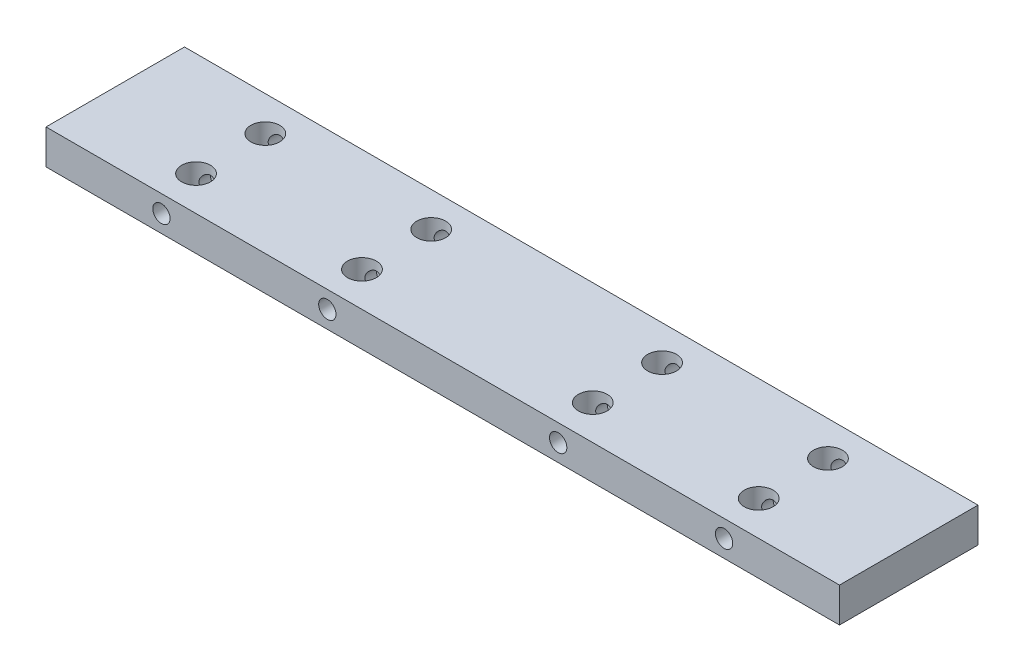
SolidWorks part; units mm, degrees
material "HDPE-green"
ref_plane "Front Plane" through (0, 0, 0) normal (0, 0, 1) x (1, 0, 0)
ref_plane "Top Plane" through (0, 0, 0) normal (0, 1, 0) x (1, 0, 0)
ref_plane "Right Plane" through (0, 0, 0) normal (1, 0, 0) x (0, 0, -1)
sketch "Sketch1" plane through (0, 0, 0) normal (0, 1, 0) x (1, 0, 0)
  line L1 (137.5, -24) -> (-137.5, -24)
  line L2 (137.5, -24) -> (137.5, 24)
  line L3 (137.5, 24) -> (-137.5, 24)
  line L4 (-137.5, -24) -> (-137.5, 24)
  line L5 (137.5, -24) -> (-137.5, 24) construction
  line L6 (137.5, 24) -> (-137.5, -24) construction
  point P0 (0, 0)
  dimension "D1" = 275
  dimension "D2" = 48
extrude "Boss-Extrude1" add sketch "Sketch1" along normal blind 12
hole_wizard "Ø10.0 (10) Diameter Hole1" positions "Sketch3" profile "Sketch2" hole size "Ø10.0" standard "ISO" end condition up to next
sketch "Sketch3" plane through (0, 12, 0) normal (0, 1, 0) x (-1, 0, 0)
  line L0 (137.5, 24) -> (-137.5, 24) construction
  line L1 (137.5, -24) -> (137.5, 24) construction
  point P0 (97.5, 12)
  point P1 (40, 12)
  point P8 (0, 24)
  dimension "D1" = 12
  dimension "D2" = 12
  dimension "D3" = 40
  dimension "D4" = 40
sketch "Sketch2" plane through (-97.5, 12, 12) normal (1, 0, 0) x (0, 0, 1)
  line L0 (0, 0) -> (0, 12.001)
  line L1 (0, 12.001) -> (5, 12.001)
  line L2 (5, 12.001) -> (5, 0)
  line L5 (5, 0) -> (0, 0)
  line L11 (0, -6.35) -> (0, 107.95) construction
  dimension "Thru Hole Dia." = 10
  dimension "Thru Hole Depth" = 12.001
hole_wizard "Ø6.0 (6) Diameter Hole1" positions "Sketch5" profile "Sketch4" hole size "Ø6.0" standard "ISO"
sketch "Sketch5" plane through (0, 0, 24) normal (0, 0, 1) x (1, 0, 0)
  line L0 (-137.5, 0) -> (137.5, 0) construction
  line L1 (-137.5, 12) -> (-137.5, 0) construction
  point P0 (-97.5, 6)
  point P1 (-40, 6)
  point P8 (0, 0)
  dimension "D1" = 6
  dimension "D2" = 6
  dimension "D3" = 40
  dimension "D4" = 40
sketch "Sketch4" plane through (-97.5, 6, 24) normal (1, 0, 0) x (0, -1, 0)
  line L0 (0, 0) -> (0, 21.8026)
  line L1 (0, 21.8026) -> (3, 20)
  line L2 (3, 20) -> (3, 0)
  line L5 (3, 0) -> (0, 0)
  line L10 (0, 21.8026) -> (-3, 20) construction
  line L11 (0, -6.35) -> (0, 107.95) construction
  dimension "Hole Dia." = 6
  dimension "Hole Depth" = 20
  dimension "Drill Angle" = 118
mirror "Mirror1" about plane through (0, 0, 0) normal (1, 0, 0) of "Ø6.0 (6) Diameter Hole1", "Ø10.0 (10) Diameter Hole1"
mirror "Mirror2" about plane through (0, 0, 0) normal (0, 0, 1) of "Mirror1"
